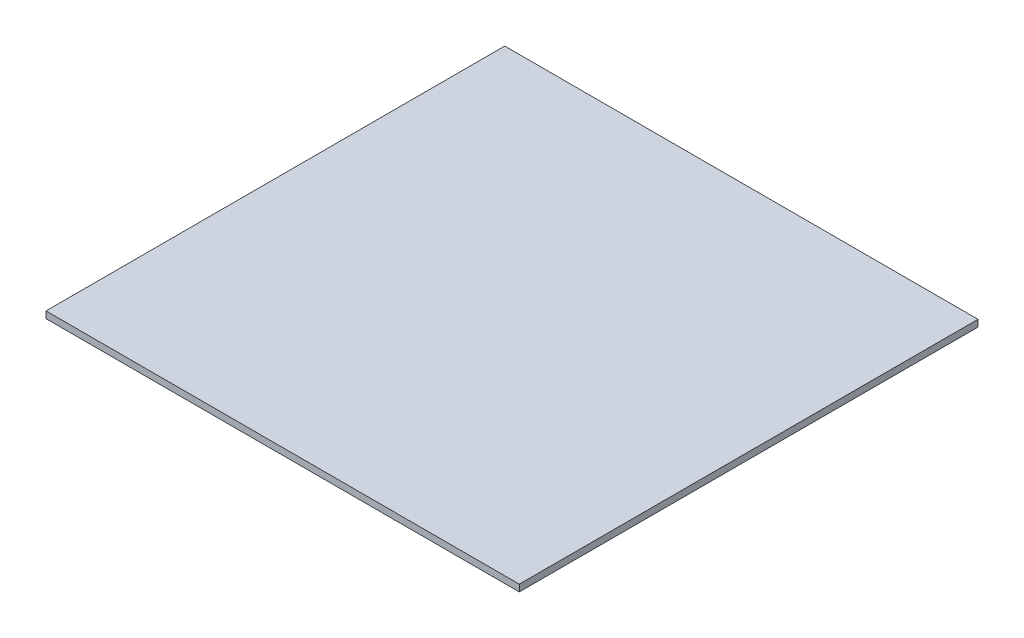
SolidWorks part; units mm, degrees
material "Polyethylene Cross-Linked"
ref_plane "Front Plane" through (0, 0, 0) normal (0, 0, 1) x (1, 0, 0)
ref_plane "Top Plane" through (0, 0, 0) normal (0, 1, 0) x (1, 0, 0)
ref_plane "Right Plane" through (0, 0, 0) normal (1, 0, 0) x (0, 0, -1)
sketch "Sketch1" plane through (0, 0, 0) normal (0, 1, 0) x (1, 0, 0)
  line L1 (0, 0) -> (222.758, 0)
  line L3 (0, 215.9) -> (222.758, 215.9)
  line L8 (222.758, 215.9) -> (222.758, 0)
  line L41 (0, 0) -> (0, 215.9)
extrude "Boss-Extrude1" add sketch "Sketch1" along normal blind 3.175
ref_plane "Plane1" through (222.758, 3.175, -215.9) normal (-1, 0, 0) x (0, 0, 1)
sketch "Sketch2" plane through (222.758, 3.175, -215.9) normal (-1, 0, 0) x (0, 0, 1)
